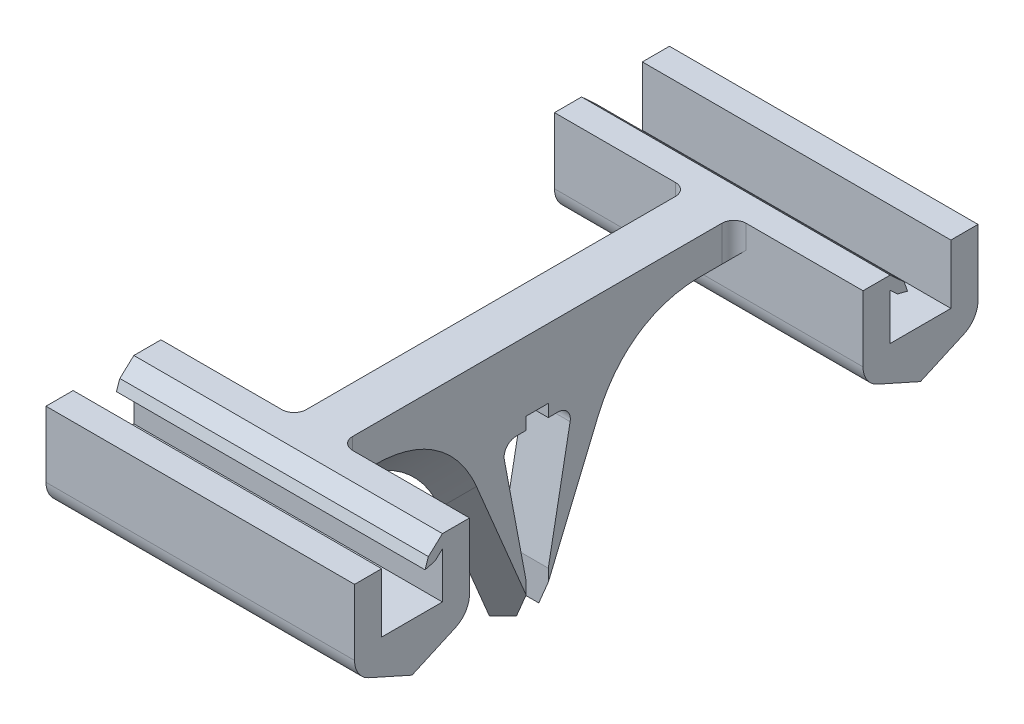
SolidWorks part; units mm, degrees
ref_plane "Front Plane" through (0, 0, 0) normal (0, 0, 1) x (1, 0, 0)
ref_plane "Top Plane" through (0, 0, 0) normal (0, 1, 0) x (1, 0, 0)
ref_plane "Right Plane" through (0, 0, 0) normal (1, 0, 0) x (0, 0, -1)
sketch "Sketch1" plane through (0, 0, 0) normal (1, 0, 0) x (0, 0, -1)
  line L0 (0, 0) -> (0, 50000) construction
  line L1 (9.214, -0.7234) -> (9.214, -0.1799) construction
  line L2 (9.9311, -1.1113) -> (9.6556, -0.8578) construction
  line L3 (9.791, -0.7106) -> (9.5201, -1.005) construction
  line L4 (9.5201, -1.005) -> (9.214, -0.7234)
  line L5 (9.9311, -1.1113) -> (9.5201, -1.005)
  line L6 (9.791, -0.7106) -> (9.9311, -1.1113)
  line L7 (9.214, -0.1799) -> (9.791, -0.7106)
  line L8 (8.0982, -0.1799) -> (8.0982, -2.8934)
  line L9 (8.6896, -3.8061) -> (10.464, -4.6005)
  line L10 (11.714, -0.1799) -> (12.8299, -0.1799)
  line L11 (11.714, -2.6173) -> (11.714, -0.1799)
  line L12 (-9.214, -0.1799) -> (-8.0982, -0.1799)
  line L13 (-9.214, -2.6173) -> (-9.214, -0.7234)
  line L14 (-11.714, -2.6173) -> (-9.214, -2.6173)
  line L15 (-12.2385, -3.8061) -> (-10.464, -4.6005)
  line L16 (-12.8299, -0.1799) -> (-12.8299, -2.8934)
  line L17 (-11.714, -2.6173) -> (-11.714, -0.1799)
  line L18 (-11.714, -0.1799) -> (-12.8299, -0.1799)
  line L19 (-8.6896, -3.8061) -> (-10.464, -4.6005)
  line L20 (-8.0982, -0.1799) -> (-8.0982, -2.8934)
  line L21 (-9.214, -0.1799) -> (-9.791, -0.7106)
  line L22 (-9.791, -0.7106) -> (-9.9311, -1.1113)
  line L23 (-9.9311, -1.1113) -> (-9.5201, -1.005)
  line L24 (-9.5201, -1.005) -> (-9.214, -0.7234)
  line L25 (-9.791, -0.7106) -> (-9.5201, -1.005) construction
  line L26 (-9.9311, -1.1113) -> (-9.6556, -0.8578) construction
  line L27 (-9.214, -0.7234) -> (-9.214, -0.1799) construction
  line L28 (12.8299, -0.1799) -> (12.8299, -2.8934)
  line L29 (12.2385, -3.8061) -> (10.464, -4.6005)
  line L30 (11.714, -2.6173) -> (9.214, -2.6173)
  line L31 (9.214, -2.6173) -> (9.214, -0.7234)
  line L32 (9.214, -0.1799) -> (8.0982, -0.1799)
  arc A0 (-8.6896, -3.8061) -> (-8.0982, -2.8934) centre (-9.0982, -2.8934) ccw
  arc A1 (-12.2385, -3.8061) -> (-12.8299, -2.8934) centre (-11.8299, -2.8934) cw
  arc A2 (12.2385, -3.8061) -> (12.8299, -2.8934) centre (11.8299, -2.8934) ccw
  arc A3 (8.6896, -3.8061) -> (8.0982, -2.8934) centre (9.0982, -2.8934) cw
  point P27 (-8.0982, -3.5413)
  point P42 (8.0982, -3.5413)
  dimension "D3" = 1
  dimension "D1" = 11.714
  dimension "D2" = 1.1159
  dimension "D4" = 0.4
  dimension "D5" = 2.7135
  dimension "D6" = 1.9442
  dimension "D7" = 1.9442
  dimension "D8" = 2.7135
  dimension "D9" = 1.1159
extrude "Boss-Extrude1" add sketch "Sketch1" along normal blind 12.7 contours L17 L18 L19 L20 L12 L13 L14
sketch "Sketch2" plane through (0, 0, -8.0982) normal (0, 0, 1) x (1, 0, 0)
  line L1 (5.4781, -0.1799) -> (7.3878, -0.1799)
  line L2 (5.4781, -0.1799) -> (5.4781, -1.6416)
  line L3 (5.4781, -1.6416) -> (7.3878, -1.6416) construction
  line L4 (7.3878, -0.1799) -> (7.3878, -1.6416)
  line L5 (5.4781, -1.6416) -> (6.433, -2.5964)
  line L6 (6.433, -2.5964) -> (7.3878, -1.6416)
  line L8 (12.7, -0.1799) -> (0, -0.1799) construction
extrude "Boss-Extrude2" add sketch "Sketch2" along normal up to next
sketch "Sketch3" plane through (5.4781, 0, 0) normal (-1, 0, 0) x (0, 0, 1)
  line L0 (0, 0) -> (0, -50000) construction
  line L1 (8.0982, -0.1799) -> (-8.0982, -0.1799) construction
  line L2 (0.456, -0.9172) -> (0.456, -0.1799)
  line L3 (-0.456, -0.9172) -> (-0.456, -0.1799)
  line L4 (-0.456, -0.1799) -> (0.456, -0.1799)
  line L5 (0.456, -0.9172) -> (-0.456, -0.9172)
  point P4 (0, -0.1799)
  dimension "D1" = 0.912
extrude "Cut-Extrude1" [suppressed] cut sketch "Sketch3" against normal up to next
sketch "Sketch4" plane through (5.4781, 0, 0) normal (-1, 0, 0) x (0, 0, 1)
  line L0 (0, 0.1001) -> (0, -49999.8999) construction
  line L1 (8.0982, -0.1799) -> (-8.0982, -0.1799) construction
  line L2 (0.8633, -3.5368) -> (0.456, -3.5368)
  line L3 (0.456, -12.0032) -> (0.456, -8.9021)
  line L4 (0.456, -3.5368) -> (0.456, -3.0284)
  line L5 (-0.456, -12.0032) -> (0.456, -12.0032)
  line L6 (0.456, -8.9021) -> (1.3546, -4.1293)
  line L7 (0.456, -3.0284) -> (-0.456, -3.0284)
  line L8 (-0.456, -8.9021) -> (-1.3546, -4.1293)
  line L9 (-0.456, -3.5368) -> (-0.456, -3.0284)
  line L10 (-0.456, -12.0032) -> (-0.456, -8.9021)
  line L11 (-0.8633, -3.5368) -> (-0.456, -3.5368)
  arc A0 (0.8633, -3.5368) -> (1.3546, -4.1293) centre (0.8633, -4.0368) cw
  arc A1 (-0.8633, -3.5368) -> (-1.3546, -4.1293) centre (-0.8633, -4.0368) ccw
  point P4 (0, -0.1799)
  point P17 (1.4662, -3.5368)
  dimension "D1" = 0.912
sketch "Sketch5" plane through (0, -0.1799, 0) normal (0, 1, 0) x (1, 0, 0)
  line L0 (7.3878, -8.0982) -> (7.3878, 8.0982) construction
  line L1 (7.3878, 4.3138) -> (5.4781, 4.3138) construction
  line L2 (7.3878, 0) -> (-49992.6122, 0) construction
  line L3 (7.3878, 4.3138) -> (7.3878, -4.3138)
  line L4 (7.3878, -4.3138) -> (5.4781, -4.3138) construction
  line L6 (7.3878, 4.3138) -> (6.433, 5.2686)
  line L7 (6.433, 5.2686) -> (5.4781, 4.3138)
  line L8 (6.433, -5.2686) -> (5.4781, -4.3138)
  line L9 (7.3878, -4.3138) -> (6.433, -5.2686)
  line L10 (5.4781, -4.3138) -> (5.4781, 4.3138)
  point P11 (7.3878, 0)
sketch3d "3DSketch1"
  dimension "D1" = 10.16
sketch "Sketch6" plane through (0, -10.3399, 0) normal (0, 1, 0) x (1, 0, 0)
  line L0 (6.433, -1.0178) -> (5.4781, -0.063)
  line L1 (200007.3878, 0) -> (-249992.6122, 0) construction
  line L2 (200007.3878, 0) -> (-249992.6122, 0)
  line L3 (7.3878, -0.063) -> (6.433, -1.0178)
  line L4 (7.3878, 0.063) -> (6.433, 1.0178)
  line L5 (6.433, 1.0178) -> (5.4781, 0.063)
  line L6 (5.4781, -0.063) -> (5.4781, 0.063)
  line L7 (7.3878, 0.063) -> (7.3878, -0.063)
  line L8 (5.4781, -4.3138) -> (5.4781, 4.3138) construction
loft "Loft4" add profiles "Sketch5", "Sketch6"
extrude "Cut-Extrude2" cut sketch "Sketch4" against normal up to next
fillet "Fillet1" radius 6.35 4 edges at (6.9104, -2.119, -3.9799) (5.9555, -2.119, -3.9799) (6.9104, -2.119, 3.9799) (5.9555, -2.119, 3.9799)
fillet "Fillet3" radius 0.5 4 edges at (7.3878, -0.9107, 8.0982) (5.4781, -0.9107, 8.0982) (7.3878, -0.9107, -8.0982) (5.4781, -0.9107, -8.0982)
